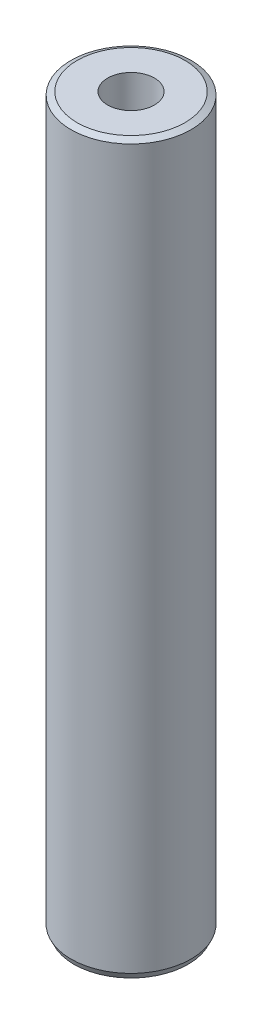
SolidWorks part; units mm, degrees
ref_plane "Front Plane" through (0, 0, 0) normal (0, 0, 1) x (1, 0, 0)
ref_plane "Top Plane" through (0, 0, 0) normal (0, 1, 0) x (1, 0, 0)
ref_plane "Right Plane" through (0, 0, 0) normal (1, 0, 0) x (0, 0, -1)
sketch "Sketch1" plane through (0, 0, 0) normal (0, 1, 0) x (1, 0, 0)
  circle A0 centre (0, 0) radius 10
  dimension "SHAFT_OD" = 20
extrude "Boss-Extrude1" add sketch "Sketch1" along normal blind 121.0872
sketch "Sketch2" plane through (0, 0, 0) normal (0, 1, 0) x (1, 0, 0)
  circle A0 centre (0, 0) radius 3.8934
  dimension "BORE_D" = 7.7868
extrude "Cut-Extrude1" cut sketch "Sketch2" along normal through all
chamfer "Chamfer1" distance 0.4984 angle 63.967 2 edges at (0, 121.0872, 10) (0, 0, 10) first distance on face at (0, 121.0872, 10) first distance on face at (0, 0, 3.8934)
